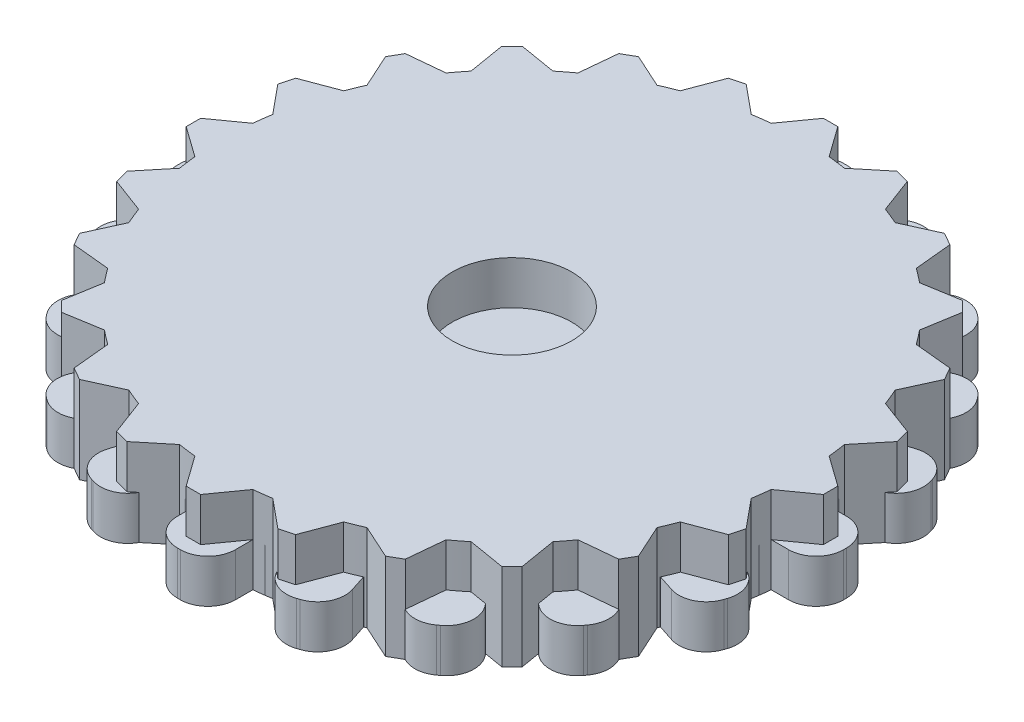
SolidWorks part; units mm, degrees
ref_plane "Front Plane" through (0, 0, 0) normal (0, 0, 1) x (1, 0, 0)
ref_plane "Top Plane" through (0, 0, 0) normal (0, 1, 0) x (1, 0, 0)
ref_plane "Right Plane" through (0, 0, 0) normal (1, 0, 0) x (0, 0, -1)
sketch "Sketch1" plane through (0, 0, 0) normal (0, 1, 0) x (1, 0, 0)
  line L111 (-0.5, 14.7462) -> (0.5, 14.7462)
  line L112 (0.5, 14.7462) -> (2, 12.5441)
  line L113 (-0.5, 14.7462) -> (-2, 12.5441)
  line L114 (6.433, 12.8885) -> (6.631, 10.2315)
  line L115 (5.567, 13.3885) -> (6.433, 12.8885)
  line L116 (5.567, 13.3885) -> (3.1669, 12.2315)
  line L117 (10.6423, 8.3132) -> (9.4853, 5.9131)
  line L118 (10.1423, 9.1792) -> (10.6423, 8.3132)
  line L119 (10.1423, 9.1792) -> (7.4853, 9.3772)
  line L120 (12, 2.2462) -> (9.798, 0.7462)
  line L121 (12, 3.2462) -> (12, 2.2462)
  line L122 (12, 3.2462) -> (9.798, 4.7462)
  line L123 (10.1423, -3.6868) -> (7.4853, -3.8849)
  line L124 (10.6423, -2.8208) -> (10.1423, -3.6868)
  line L125 (10.6423, -2.8208) -> (9.4853, -0.4208)
  line L126 (5.567, -7.8961) -> (3.1669, -6.7391)
  line L127 (6.433, -7.3961) -> (5.567, -7.8961)
  line L128 (6.433, -7.3961) -> (6.631, -4.7391)
  line L129 (-0.5, -9.2538) -> (-2, -7.0518)
  line L130 (0.5, -9.2538) -> (-0.5, -9.2538)
  line L131 (0.5, -9.2538) -> (2, -7.0518)
  line L132 (-6.433, -7.3961) -> (-6.631, -4.7391)
  line L133 (-5.567, -7.8961) -> (-6.433, -7.3961)
  line L134 (-5.567, -7.8961) -> (-3.1669, -6.7391)
  line L135 (-10.6423, -2.8208) -> (-9.4853, -0.4208)
  line L136 (-10.1423, -3.6868) -> (-10.6423, -2.8208)
  line L137 (-10.1423, -3.6868) -> (-7.4853, -3.8849)
  line L138 (-12, 3.2462) -> (-9.798, 4.7462)
  line L139 (-12, 2.2462) -> (-12, 3.2462)
  line L140 (-12, 2.2462) -> (-9.798, 0.7462)
  line L141 (-10.1423, 9.1792) -> (-7.4853, 9.3772)
  line L142 (-10.6423, 8.3132) -> (-10.1423, 9.1792)
  line L143 (-10.6423, 8.3132) -> (-9.4853, 5.9131)
  line L144 (-5.567, 13.3885) -> (-3.1669, 12.2315)
  line L145 (-6.433, 12.8885) -> (-5.567, 13.3885)
  line L146 (-6.433, 12.8885) -> (-6.631, 10.2315)
  arc A43 (-2, 12.5441) -> (-3.1669, 12.2315) centre (0, 2.7462) ccw
  arc A44 (-6.631, 10.2315) -> (-7.4853, 9.3772) centre (0, 2.7462) ccw
  arc A45 (-9.4853, 5.9131) -> (-9.798, 4.7462) centre (0, 2.7462) ccw
  arc A46 (-9.798, 0.7462) -> (-9.4853, -0.4208) centre (0, 2.7462) ccw
  arc A47 (-7.4853, -3.8849) -> (-6.631, -4.7391) centre (0, 2.7462) ccw
  arc A48 (-3.1669, -6.7391) -> (-2, -7.0518) centre (0, 2.7462) ccw
  arc A49 (2, -7.0518) -> (3.1669, -6.7391) centre (0, 2.7462) ccw
  arc A50 (6.631, -4.7391) -> (7.4853, -3.8849) centre (0, 2.7462) ccw
  arc A51 (9.4853, -0.4208) -> (9.798, 0.7462) centre (0, 2.7462) ccw
  arc A52 (9.798, 4.7462) -> (9.4853, 5.9131) centre (0, 2.7462) ccw
  arc A53 (7.4853, 9.3772) -> (6.631, 10.2315) centre (0, 2.7462) ccw
  arc A54 (3.1669, 12.2315) -> (2, 12.5441) centre (0, 2.7462) ccw
  point P6 (0, 0)
  point P8 (0, 0)
  point P9 (0, 0)
  point P12 (0, 2.7462)
  point P17 (0, 0)
  point P18 (0, 2.7462)
  point P22 (-2.5, 0.7462)
  point P63 (0, 0)
  point P68 (0, 0)
  point P69 (0, 2.7462)
  point P119 (0, 0)
  dimension "D1" = 20
  dimension "D8" = 12
sketch "Sketch2" plane through (0, 0, 0) normal (0, 1, 0) x (1, 0, 0)
  line L0 (-2, 0) -> (2, 0)
  line L1 (-23, -0.1) -> (-23, 0.1)
  line L2 (-21.1, 2) -> (-19.8997, 2)
  line L3 (-21.1, -2) -> (-19.8997, -2)
  line L4 (-20.6853, 4.6181) -> (-19.5438, 4.2472)
  line L5 (-19.4493, 8.4224) -> (-18.3078, 8.0515)
  line L6 (-21.9052, 7.0123) -> (-21.8434, 7.2025)
  line L7 (-18.2458, 10.7842) -> (-17.2748, 10.0787)
  line L8 (-15.8947, 14.0203) -> (-14.9237, 13.3148)
  line L9 (-18.6662, 13.4382) -> (-18.5486, 13.6)
  line L10 (-14.0203, 15.8947) -> (-13.3148, 14.9237)
  line L11 (-10.7842, 18.2458) -> (-10.0787, 17.2748)
  line L12 (-13.6, 18.5486) -> (-13.4382, 18.6662)
  line L13 (-8.4224, 19.4493) -> (-8.0515, 18.3078)
  line L14 (-4.6181, 20.6853) -> (-4.2472, 19.5438)
  line L15 (-7.2025, 21.8434) -> (-7.0123, 21.9052)
  line L16 (-2, 21.1) -> (-2, 19.8997)
  line L17 (2, 21.1) -> (2, 19.8997)
  line L18 (-0.1, 23) -> (0.1, 23)
  line L19 (4.6181, 20.6853) -> (4.2472, 19.5438)
  line L20 (8.4224, 19.4493) -> (8.0515, 18.3078)
  line L21 (7.0123, 21.9052) -> (7.2025, 21.8434)
  line L22 (10.7842, 18.2458) -> (10.0787, 17.2748)
  line L23 (14.0203, 15.8947) -> (13.3148, 14.9237)
  line L24 (13.4382, 18.6662) -> (13.6, 18.5486)
  line L25 (15.8947, 14.0203) -> (14.9237, 13.3148)
  line L26 (18.2458, 10.7842) -> (17.2748, 10.0787)
  line L27 (18.5486, 13.6) -> (18.6662, 13.4382)
  line L28 (19.4493, 8.4224) -> (18.3078, 8.0515)
  line L29 (20.6853, 4.6181) -> (19.5438, 4.2472)
  line L30 (21.8434, 7.2025) -> (21.9052, 7.0123)
  line L31 (21.1, 2) -> (19.8997, 2)
  line L32 (21.1, -2) -> (19.8997, -2)
  line L33 (23, 0.1) -> (23, -0.1)
  line L34 (20.6853, -4.6181) -> (19.5438, -4.2472)
  line L35 (19.4493, -8.4224) -> (18.3078, -8.0515)
  line L36 (21.9052, -7.0123) -> (21.8434, -7.2025)
  line L37 (18.2458, -10.7842) -> (17.2748, -10.0787)
  line L38 (15.8947, -14.0203) -> (14.9237, -13.3148)
  line L39 (18.6662, -13.4382) -> (18.5486, -13.6)
  line L40 (14.0203, -15.8947) -> (13.3148, -14.9237)
  line L41 (10.7842, -18.2458) -> (10.0787, -17.2748)
  line L42 (13.6, -18.5486) -> (13.4382, -18.6662)
  line L43 (8.4224, -19.4493) -> (8.0515, -18.3078)
  line L44 (4.6181, -20.6853) -> (4.2472, -19.5438)
  line L45 (7.2025, -21.8434) -> (7.0123, -21.9052)
  line L46 (2, -21.1) -> (2, -19.8997)
  line L47 (-2, -21.1) -> (-2, -19.8997)
  line L48 (0.1, -23) -> (-0.1, -23)
  line L49 (-4.6181, -20.6853) -> (-4.2472, -19.5438)
  line L50 (-8.4224, -19.4493) -> (-8.0515, -18.3078)
  line L51 (-7.0123, -21.9052) -> (-7.2025, -21.8434)
  line L52 (-10.7842, -18.2458) -> (-10.0787, -17.2748)
  line L53 (-14.0203, -15.8947) -> (-13.3148, -14.9237)
  line L54 (-13.4382, -18.6662) -> (-13.6, -18.5486)
  line L55 (-15.8947, -14.0203) -> (-14.9237, -13.3148)
  line L56 (-18.2458, -10.7842) -> (-17.2748, -10.0787)
  line L57 (-18.5486, -13.6) -> (-18.6662, -13.4382)
  line L58 (-19.4493, -8.4224) -> (-18.3078, -8.0515)
  line L59 (-20.6853, -4.6181) -> (-19.5438, -4.2472)
  line L60 (-21.8434, -7.2025) -> (-21.9052, -7.0123)
  arc A0 (-18.3078, -8.0515) -> (-17.2748, -10.0787) centre (0, 0) ccw
  arc A1 (-21.1, 2) -> (-23, 0.1) centre (-21.1, 0.1) ccw
  arc A2 (-21.1, -2) -> (-23, -0.1) centre (-21.1, -0.1) cw
  arc A3 (-20.6853, 4.6181) -> (-21.9052, 7.0123) centre (-20.0982, 6.4252) cw
  arc A4 (-19.4493, 8.4224) -> (-21.8434, 7.2025) centre (-20.0364, 6.6154) ccw
  arc A5 (-18.2458, 10.7842) -> (-18.6662, 13.4382) centre (-17.129, 12.3214) cw
  arc A6 (-15.8947, 14.0203) -> (-18.5486, 13.6) centre (-17.0115, 12.4832) ccw
  arc A7 (-14.0203, 15.8947) -> (-13.6, 18.5486) centre (-12.4832, 17.0115) cw
  arc A8 (-10.7842, 18.2458) -> (-13.4382, 18.6662) centre (-12.3214, 17.129) ccw
  arc A9 (-8.4224, 19.4493) -> (-7.2025, 21.8434) centre (-6.6154, 20.0364) cw
  arc A10 (-4.6181, 20.6853) -> (-7.0123, 21.9052) centre (-6.4252, 20.0982) ccw
  arc A11 (-2, 21.1) -> (-0.1, 23) centre (-0.1, 21.1) cw
  arc A12 (2, 21.1) -> (0.1, 23) centre (0.1, 21.1) ccw
  arc A13 (4.6181, 20.6853) -> (7.0123, 21.9052) centre (6.4252, 20.0982) cw
  arc A14 (8.4224, 19.4493) -> (7.2025, 21.8434) centre (6.6154, 20.0364) ccw
  arc A15 (10.7842, 18.2458) -> (13.4382, 18.6662) centre (12.3214, 17.129) cw
  arc A16 (14.0203, 15.8947) -> (13.6, 18.5486) centre (12.4832, 17.0115) ccw
  arc A17 (15.8947, 14.0203) -> (18.5486, 13.6) centre (17.0115, 12.4832) cw
  arc A18 (18.2458, 10.7842) -> (18.6662, 13.4382) centre (17.129, 12.3214) ccw
  arc A19 (19.4493, 8.4224) -> (21.8434, 7.2025) centre (20.0364, 6.6154) cw
  arc A20 (20.6853, 4.6181) -> (21.9052, 7.0123) centre (20.0982, 6.4252) ccw
  arc A21 (21.1, 2) -> (23, 0.1) centre (21.1, 0.1) cw
  arc A22 (21.1, -2) -> (23, -0.1) centre (21.1, -0.1) ccw
  arc A23 (20.6853, -4.6181) -> (21.9052, -7.0123) centre (20.0982, -6.4252) cw
  arc A24 (19.4493, -8.4224) -> (21.8434, -7.2025) centre (20.0364, -6.6154) ccw
  arc A25 (18.2458, -10.7842) -> (18.6662, -13.4382) centre (17.129, -12.3214) cw
  arc A26 (15.8947, -14.0203) -> (18.5486, -13.6) centre (17.0115, -12.4832) ccw
  arc A27 (14.0203, -15.8947) -> (13.6, -18.5486) centre (12.4832, -17.0115) cw
  arc A28 (10.7842, -18.2458) -> (13.4382, -18.6662) centre (12.3214, -17.129) ccw
  arc A29 (8.4224, -19.4493) -> (7.2025, -21.8434) centre (6.6154, -20.0364) cw
  arc A30 (4.6181, -20.6853) -> (7.0123, -21.9052) centre (6.4252, -20.0982) ccw
  arc A31 (2, -21.1) -> (0.1, -23) centre (0.1, -21.1) cw
  arc A32 (-2, -21.1) -> (-0.1, -23) centre (-0.1, -21.1) ccw
  arc A33 (-4.6181, -20.6853) -> (-7.0123, -21.9052) centre (-6.4252, -20.0982) cw
  arc A34 (-8.4224, -19.4493) -> (-7.2025, -21.8434) centre (-6.6154, -20.0364) ccw
  arc A35 (-10.7842, -18.2458) -> (-13.4382, -18.6662) centre (-12.3214, -17.129) cw
  arc A36 (-14.0203, -15.8947) -> (-13.6, -18.5486) centre (-12.4832, -17.0115) ccw
  arc A37 (-15.8947, -14.0203) -> (-18.5486, -13.6) centre (-17.0115, -12.4832) cw
  arc A38 (-18.2458, -10.7842) -> (-18.6662, -13.4382) centre (-17.129, -12.3214) ccw
  arc A39 (-19.4493, -8.4224) -> (-21.8434, -7.2025) centre (-20.0364, -6.6154) cw
  arc A40 (-20.6853, -4.6181) -> (-21.9052, -7.0123) centre (-20.0982, -6.4252) ccw
  arc A41 (-19.8997, -2) -> (-19.5438, -4.2472) centre (0, 0) ccw
  arc A42 (-19.5438, 4.2472) -> (-19.8997, 2) centre (0, 0) ccw
  arc A43 (-17.2748, 10.0787) -> (-18.3078, 8.0515) centre (0, 0) ccw
  arc A44 (-13.3148, 14.9237) -> (-14.9237, 13.3148) centre (0, 0) ccw
  arc A45 (-8.0515, 18.3078) -> (-10.0787, 17.2748) centre (0, 0) ccw
  arc A46 (-2, 19.8997) -> (-4.2472, 19.5438) centre (0, 0) ccw
  arc A47 (4.2472, 19.5438) -> (2, 19.8997) centre (0, 0) ccw
  arc A48 (10.0787, 17.2748) -> (8.0515, 18.3078) centre (0, 0) ccw
  arc A49 (14.9237, 13.3148) -> (13.3148, 14.9237) centre (0, 0) ccw
  arc A50 (18.3078, 8.0515) -> (17.2748, 10.0787) centre (0, 0) ccw
  arc A51 (19.8997, 2) -> (19.5438, 4.2472) centre (0, 0) ccw
  arc A52 (19.5438, -4.2472) -> (19.8997, -2) centre (0, 0) ccw
  arc A53 (17.2748, -10.0787) -> (18.3078, -8.0515) centre (0, 0) ccw
  arc A54 (13.3148, -14.9237) -> (14.9237, -13.3148) centre (0, 0) ccw
  arc A55 (8.0515, -18.3078) -> (10.0787, -17.2748) centre (0, 0) ccw
  arc A56 (2, -19.8997) -> (4.2472, -19.5438) centre (0, 0) ccw
  arc A57 (-10.0787, -17.2748) -> (-8.0515, -18.3078) centre (0, 0) ccw
  arc A58 (-4.2472, -19.5438) -> (-2, -19.8997) centre (0, 0) ccw
  arc A59 (-14.9237, -13.3148) -> (-13.3148, -14.9237) centre (0, 0) ccw
  point P6 (0, 0)
  point P10 (-23, 2)
  point P170 (0, 0)
  dimension "D1" = 40
  dimension "D4" = 1.9
  dimension "D5" = 20
extrude "Boss-Extrude3" add sketch "Sketch2" along normal blind 3 contours L55 A59 L53 A36 L54 A35 L52 A57 L50 A34 L51 A33 L49 A58 L47 A32 L48 A31 L46 A56 L44 A30 L45 A29 L43 A55 L41 A28 L42 A27 L40 A54 L38 A26 L39 A25 L37 A53 L35 A24 L36 A23 L34 A52 L32 A22 L33 A21 region at (-22.3495, 0, 0)
sketch "Sketch3" plane through (0, 0, 0) normal (0, 1, 0) x (1, 0, 0)
  line L0 (-22, 0) -> (22, 0)
  line L1 (22, -0.5) -> (22, 0.5)
  line L2 (22, 0.5) -> (19.8997, 2)
  line L3 (22, -0.5) -> (19.8997, -2)
  line L4 (21.3798, -5.2111) -> (19.7393, -3.2186)
  line L5 (21.121, -6.177) -> (21.3798, -5.2111)
  line L6 (21.121, -6.177) -> (18.704, -7.0823)
  line L7 (19.3026, -10.567) -> (18.2337, -8.2178)
  line L8 (18.8026, -11.433) -> (19.3026, -10.567)
  line L9 (18.8026, -11.433) -> (16.2337, -11.6819)
  line L10 (15.9099, -15.2028) -> (15.4855, -12.657)
  line L11 (15.2028, -15.9099) -> (15.9099, -15.2028)
  line L12 (15.2028, -15.9099) -> (12.657, -15.4855)
  line L13 (11.433, -18.8026) -> (11.6819, -16.2337)
  line L14 (10.567, -19.3026) -> (11.433, -18.8026)
  line L15 (10.567, -19.3026) -> (8.2178, -18.2337)
  line L16 (6.177, -21.121) -> (7.0823, -18.704)
  line L17 (5.2111, -21.3798) -> (6.177, -21.121)
  line L18 (5.2111, -21.3798) -> (3.2186, -19.7393)
  line L19 (0.5, -22) -> (2, -19.8997)
  line L20 (-0.5, -22) -> (0.5, -22)
  line L21 (-0.5, -22) -> (-2, -19.8997)
  line L22 (-5.2111, -21.3798) -> (-3.2186, -19.7393)
  line L23 (-6.177, -21.121) -> (-5.2111, -21.3798)
  line L24 (-6.177, -21.121) -> (-7.0823, -18.704)
  line L25 (-10.567, -19.3026) -> (-8.2178, -18.2337)
  line L26 (-11.433, -18.8026) -> (-10.567, -19.3026)
  line L27 (-11.433, -18.8026) -> (-11.6819, -16.2337)
  line L28 (-15.2028, -15.9099) -> (-12.657, -15.4855)
  line L29 (-15.9099, -15.2028) -> (-15.2028, -15.9099)
  line L30 (-15.9099, -15.2028) -> (-15.4855, -12.657)
  line L31 (-18.8026, -11.433) -> (-16.2337, -11.6819)
  line L32 (-19.3026, -10.567) -> (-18.8026, -11.433)
  line L33 (-19.3026, -10.567) -> (-18.2337, -8.2178)
  line L34 (-21.121, -6.177) -> (-18.704, -7.0823)
  line L35 (-21.3798, -5.2111) -> (-21.121, -6.177)
  line L36 (-21.3798, -5.2111) -> (-19.7393, -3.2186)
  line L37 (-22, -0.5) -> (-19.8997, -2)
  line L38 (-22, 0.5) -> (-22, -0.5)
  line L39 (-22, 0.5) -> (-19.8997, 2)
  line L40 (-21.3798, 5.2111) -> (-19.7393, 3.2186)
  line L41 (-21.121, 6.177) -> (-21.3798, 5.2111)
  line L42 (-21.121, 6.177) -> (-18.704, 7.0823)
  line L43 (-19.3026, 10.567) -> (-18.2337, 8.2178)
  line L44 (-18.8026, 11.433) -> (-19.3026, 10.567)
  line L45 (-18.8026, 11.433) -> (-16.2337, 11.6819)
  line L46 (-15.9099, 15.2028) -> (-15.4855, 12.657)
  line L47 (-15.2028, 15.9099) -> (-15.9099, 15.2028)
  line L48 (-15.2028, 15.9099) -> (-12.657, 15.4855)
  line L49 (-11.433, 18.8026) -> (-11.6819, 16.2337)
  line L50 (-10.567, 19.3026) -> (-11.433, 18.8026)
  line L51 (-10.567, 19.3026) -> (-8.2178, 18.2337)
  line L52 (-6.177, 21.121) -> (-7.0823, 18.704)
  line L53 (-5.2111, 21.3798) -> (-6.177, 21.121)
  line L54 (-5.2111, 21.3798) -> (-3.2186, 19.7393)
  line L55 (-0.5, 22) -> (-2, 19.8997)
  line L56 (0.5, 22) -> (-0.5, 22)
  line L57 (0.5, 22) -> (2, 19.8997)
  line L58 (5.2111, 21.3798) -> (3.2186, 19.7393)
  line L59 (6.177, 21.121) -> (5.2111, 21.3798)
  line L60 (6.177, 21.121) -> (7.0823, 18.704)
  line L61 (10.567, 19.3026) -> (8.2178, 18.2337)
  line L62 (11.433, 18.8026) -> (10.567, 19.3026)
  line L63 (11.433, 18.8026) -> (11.6819, 16.2337)
  line L64 (15.2028, 15.9099) -> (12.657, 15.4855)
  line L65 (15.9099, 15.2028) -> (15.2028, 15.9099)
  line L66 (15.9099, 15.2028) -> (15.4855, 12.657)
  line L67 (18.8026, 11.433) -> (16.2337, 11.6819)
  line L68 (19.3026, 10.567) -> (18.8026, 11.433)
  line L69 (19.3026, 10.567) -> (18.2337, 8.2178)
  line L70 (21.121, 6.177) -> (18.704, 7.0823)
  line L71 (21.3798, 5.2111) -> (21.121, 6.177)
  line L72 (21.3798, 5.2111) -> (19.7393, 3.2186)
  arc A0 (-8.2178, -18.2337) -> (-7.0823, -18.704) centre (0, 0) ccw
  arc A1 (-12.657, -15.4855) -> (-11.6819, -16.2337) centre (0, 0) ccw
  arc A2 (-16.2337, -11.6819) -> (-15.4855, -12.657) centre (0, 0) ccw
  arc A3 (-18.704, -7.0823) -> (-18.2337, -8.2178) centre (0, 0) ccw
  arc A4 (-19.8997, -2) -> (-19.7393, -3.2186) centre (0, 0) ccw
  arc A5 (-19.7393, 3.2186) -> (-19.8997, 2) centre (0, 0) ccw
  arc A6 (-18.2337, 8.2178) -> (-18.704, 7.0823) centre (0, 0) ccw
  arc A7 (-15.4855, 12.657) -> (-16.2337, 11.6819) centre (0, 0) ccw
  arc A8 (-11.6819, 16.2337) -> (-12.657, 15.4855) centre (0, 0) ccw
  arc A9 (-7.0823, 18.704) -> (-8.2178, 18.2337) centre (0, 0) ccw
  arc A10 (-2, 19.8997) -> (-3.2186, 19.7393) centre (0, 0) ccw
  arc A11 (3.2186, 19.7393) -> (2, 19.8997) centre (0, 0) ccw
  arc A12 (8.2178, 18.2337) -> (7.0823, 18.704) centre (0, 0) ccw
  arc A13 (12.657, 15.4855) -> (11.6819, 16.2337) centre (0, 0) ccw
  arc A14 (16.2337, 11.6819) -> (15.4855, 12.657) centre (0, 0) ccw
  arc A15 (18.704, 7.0823) -> (18.2337, 8.2178) centre (0, 0) ccw
  arc A16 (19.8997, 2) -> (19.7393, 3.2186) centre (0, 0) ccw
  arc A17 (19.7393, -3.2186) -> (19.8997, -2) centre (0, 0) ccw
  arc A18 (18.2337, -8.2178) -> (18.704, -7.0823) centre (0, 0) ccw
  arc A19 (-3.2186, -19.7393) -> (-2, -19.8997) centre (0, 0) ccw
  arc A20 (2, -19.8997) -> (3.2186, -19.7393) centre (0, 0) ccw
  arc A21 (7.0823, -18.704) -> (8.2178, -18.2337) centre (0, 0) ccw
  arc A22 (11.6819, -16.2337) -> (12.657, -15.4855) centre (0, 0) ccw
  arc A23 (15.4855, -12.657) -> (16.2337, -11.6819) centre (0, 0) ccw
  point P6 (0, 0)
  point P7 (0, -12.952)
  point P8 (-6.2727, 0)
  point P9 (11.4668, 0)
  point P10 (0, 0)
  point P108 (0, 0)
  dimension "D1" = 40
  dimension "D2" = 22
  dimension "D3" = 2
  dimension "D4" = 24
extrude "Boss-Extrude5" add sketch "Sketch3" along normal blind 6 separate body contours L2 A16 L72 L71 L70 A15 L69 L68 L67 A14 L66 L65 L64 A13 L63 L62 L61 A12 L60 L59 L58 A11 L57 L56 L55 A10 L54 L53 L52 A9 L51 L50 L49 A8 L48 L47 L46 A7 L45 L44 L43 A6 L42 L41 L40 A5 L39 L38 L0 L1 | L10 A23 L9 L8 L7 A18 L6 L5 L4 A17 L3 L1 L0 L38 L37 A4 L36 L35 L34 A3 L33 L32 L31 A2 L30 L29 L28 A1 L27 L26 L25 A0 L24 L23 L22 A19 L21 L20 L19 A20 L18 L17 L16 A21 L15 L14 L13 A22 L12 L11 region at (0, 0, -8.8989) region at (0, 0, 8.8989)
extrude "Boss-Extrude6" add sketch "Sketch1" along normal blind 3 separate body
sketch "Sketch4" plane through (0, 6, 0) normal (0, 1, 0) x (1, 0, 0)
  circle A0 centre (0, 0) radius 4.125
  dimension "D1" = 8.25
extrude "Cut-Extrude1" cut sketch "Sketch4" against normal blind 10
